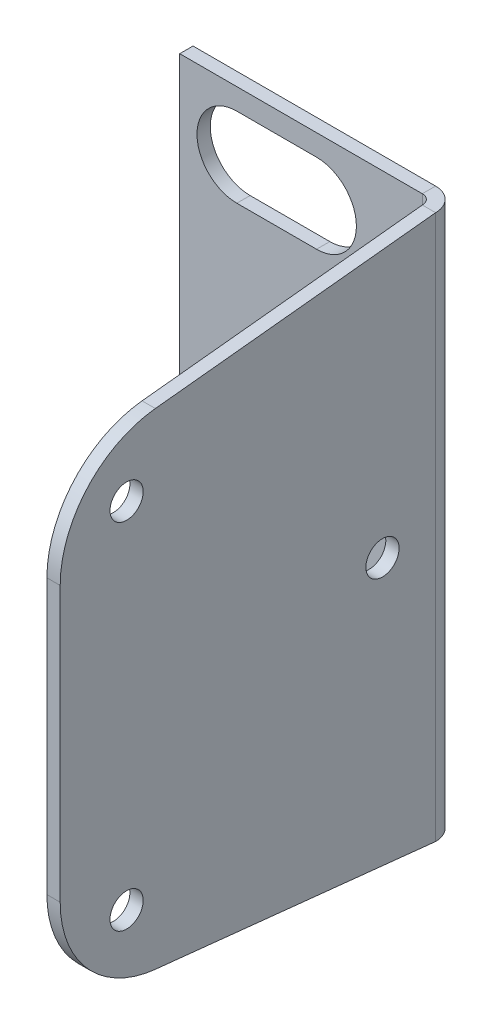
SolidWorks part; units mm, degrees
note: The reader was unsure of these and kept them because the rebuilt part matched: flange length of "Edge-Flange1".
ref_plane "Front Plane" through (0, 0, 0) normal (0, 0, 1) x (1, 0, 0)
ref_plane "Top Plane" through (0, 0, 0) normal (0, 1, 0) x (1, 0, 0)
ref_plane "Right Plane" through (0, 0, 0) normal (1, 0, 0) x (0, 0, -1)
sketch "Sketch1" plane through (0, 0, 0) normal (0, 0, 1) x (1, 0, 0)
  line L0 (-230.3, 22) -> (-230.3, -22) construction
  line L1 (-239.8, 20.5) -> (-219.8, 20.5)
  line L2 (-239.8, 20.5) -> (-239.8, 0)
  line L3 (-239.8, 0) -> (-219.8, 0)
  line L4 (-219.8, 20.5) -> (-219.8, 0)
  line L5 (-219.3, 22) -> (-241.3, 22) construction
  line L6 (-219.3, -22) -> (-241.3, -22) construction
  line L7 (-241.3, 22) -> (-241.3, -22) construction
  line L8 (-219.8, 19.2634) -> (-219.8, -19.2634) construction
  point P10 (-230.3, 0)
  dimension "D1" = 1.5
  dimension "D2" = 1.5
base flange "Base-Flange1" sketch "Sketch1" thickness 1 reverse thickness direction yes parameters "D1"=0.7366
edge flange "Edge-Flange1" sketch "Sketch8" flange angle 90 flange length 30 flange position material inside bend radius 0.7366 thickness 1 relief rectangular parameters "D6"=10
sketch "Sketch8" plane through (-219.8, 0, 1) normal (1, 0, 0) x (0, 1, 0)
  line L2 (0, 0) -> (0, 29)
  line L3 (0, 29) -> (20.5, 29)
  line L4 (20.5, 29) -> (20.5, 0)
  line L5 (0, 0) -> (20.5, 0) construction
  line L6 (0, 0) -> (20.5, 0)
bend "EdgeBend1" bend radius 0.7366 bend angle 90 parameters "D5"=1
sketch "Sketch9" plane through (-220.8, 0, 0) normal (-1, 0, 0) x (0, 0, 1)
  line L0 (1.7366, 20.5) -> (22.8362, 18.2823)
  line L1 (30, 20.5) -> (30, 0) construction
  line L2 (30, 10.3262) -> (30, 0)
  line L3 (1.7366, 20.5) -> (30, 20.5) construction
  arc A0 (30, 10.3262) -> (22.8362, 18.2823) centre (22, 10.3262) ccw
  point P9 (30, 17.5294)
  dimension "D1" = 8
  dimension "D2" = 6
extrude "Cut-Extrude1" cut sketch "Sketch9" against normal blind 10 and the other way through all
sketch "Sketch11" plane through (0, 0, 1) normal (0, 0, 1) x (1, 0, 0)
  line L0 (-229.5, 18.9) -> (-235.5, 18.9) construction
  line L1 (-235.5, 12.9) -> (-229.5, 12.9) construction
  line L2 (-229.5, 18.9) -> (-235.5, 18.9)
  line L3 (-235.5, 12.9) -> (-229.5, 12.9)
  arc A0 (-235.5, 18.9) -> (-235.5, 12.9) centre (-235.5, 15.9) ccw construction
  arc A1 (-229.5, 12.9) -> (-229.5, 18.9) centre (-229.5, 15.9) ccw construction
  arc A2 (-235.5, 18.9) -> (-235.5, 12.9) centre (-235.5, 15.9) ccw
  arc A3 (-229.5, 12.9) -> (-229.5, 18.9) centre (-229.5, 15.9) ccw
extrude "Cut-Extrude2" cut sketch "Sketch11" against normal blind 1 normal cut yes
mirror "Mirror1" about plane through (-239.8, 0, 1) normal (0, 1, 0) of bodies 104
hole_wizard "M3 Tapped Hole1" positions "Sketch13" profile "Sketch14" tap size "M3" standard "ISO" end condition through all
sketch "Sketch13" plane through (-220.8, 0, 0) normal (-1, 0, 0) x (0, 0, 1)
  line L0 (0, 0) -> (30, 0) construction
  line L1 (30, 10.3262) -> (30, -10.3262) construction
  line L2 (30, 10.3262) -> (22, 10.3262) construction
  line L3 (22, 10.3262) -> (25, 13.3262) construction
  line L4 (1.7366, -20.5) -> (1.7366, 20.5) construction
  point P0 (5.7366, 0)
  point P10 (25, 13.3262)
  point P30 (25, -13.3262)
  dimension "D3" = 4
  dimension "D1" = 45
  dimension "D2" = 5
sketch "Sketch14" plane through (-220.8, 0, 5.7366) normal (0, 1, 0) x (0, 0, 1)
  line L0 (0, 0) -> (0, 1)
  line L1 (0, 1) -> (1.25, 1)
  line L2 (1.25, 1) -> (1.25, 0)
  line L5 (1.25, 0) -> (0, 0)
  line L11 (0, -6.35) -> (0, 107.95) construction
  dimension "Thread Major Dia." = 2.5
  dimension "Thru Tap Drill Depth" = 1
sketch "Bend-Lines1" [suppressed] plane through (0, 0, 0) normal (0, 1, 0) x (1, 0, 0)
sketch "Bounding-Box1" [suppressed] plane through (0, 0, 0) normal (0, 1, 0) x (1, 0, 0)
sheet metal parameters "Sheet-Metal1" thickness 1 parameters "D1"=0.7366
flat pattern "Flat-Pattern1" [suppressed]
sketch "Bend-Lines2" plane through (0, 0, 0) normal (0, 1, 0) x (1, 0, 0)
sketch3d "Bounding-Box2" [suppressed]
  line L0 (-220.8, 20.5, 0) -> (-220.8, 0, 0) construction
  line L1 (-239.8, 20.5, 0) -> (-239.8, 0, 0) construction
  line L2 (-220.8, 20.5, 0) -> (-239.8, 20.5, 0) construction
  line L3 (-220.8, 0, 0) -> (-239.8, 0, 0) construction
sheet metal parameters "Sheet-Metal2" thickness 1 parameters "D1"=0.7366
flat pattern "Flat-Pattern1"
sketch "Bend-Lines2" plane through (0, 0, 0) normal (0, 0, -1) x (-1, 0, 0)
  line L0 (221.5654, 20.5) -> (221.5654, 0) construction
  line L1 (221.5654, 20.5) -> (221.5654, 0) construction
sketch3d "Bounding-Box2" [suppressed]
  line L0 (239.8, 0, 0) -> (192.3308, 0, 0) construction
  line L1 (239.8, 20.5, 0) -> (192.3308, 20.5, 0) construction
  line L2 (239.8, 0, 0) -> (239.8, 20.5, 0) construction
  line L3 (192.3308, 0, 0) -> (192.3308, 20.5, 0) construction
bend of the flat pattern "Flatten-<EdgeBend1>1"
sheet metal parameters "Sheet-Metal3" thickness 1 parameters "D1"=0.7366
flat pattern "Flat-Pattern1"
sketch "Bend-Lines2" plane through (0, 0, 0) normal (0, 0, -1) x (-1, 0, 0)
  line L0 (221.5654, 20.5) -> (221.5654, 0) construction
  line L1 (221.5654, 20.5) -> (221.5654, 0) construction
sketch3d "Bounding-Box2" [suppressed]
  line L0 (239.8, 0, 0) -> (192.3308, 0, 0) construction
  line L1 (239.8, 20.5, 0) -> (192.3308, 20.5, 0) construction
  line L2 (239.8, 0, 0) -> (239.8, 20.5, 0) construction
  line L3 (192.3308, 0, 0) -> (192.3308, 20.5, 0) construction
bend of the flat pattern "Flatten-<EdgeBend1>1"
sheet metal parameters "Sheet-Metal4" thickness 1 parameters "D1"=0.7366
flat pattern "Flat-Pattern1"
sketch "Bend-Lines2" plane through (0, 0, 0) normal (0, 0, -1) x (-1, 0, 0)
  line L0 (221.5654, 20.5) -> (221.5654, 0) construction
  line L1 (221.5654, 20.5) -> (221.5654, 0) construction
sketch3d "Bounding-Box2" [suppressed]
  line L0 (239.8, 0, 0) -> (192.3308, 0, 0) construction
  line L1 (239.8, 20.5, 0) -> (192.3308, 20.5, 0) construction
  line L2 (239.8, 0, 0) -> (239.8, 20.5, 0) construction
  line L3 (192.3308, 0, 0) -> (192.3308, 20.5, 0) construction
bend of the flat pattern "Flatten-<EdgeBend1>1"
sheet metal parameters "Sheet-Metal5" thickness 1 parameters "D1"=0.7366
flat pattern "Flat-Pattern5"
sketch "Bend-Lines3" plane through (0, 0, 0) normal (0, 0, -1) x (-1, 0, 0)
  line L0 (221.5654, 20.5) -> (221.5654, -20.5) construction
  line L1 (221.5654, 20.5) -> (221.5654, -20.5) construction
sketch3d "Bounding-Box3" [suppressed]
  line L0 (239.8, 20.5, 0) -> (192.3308, 20.5, 0) construction
  line L1 (239.8, -20.5, 0) -> (192.3308, -20.5, 0) construction
  line L2 (239.8, 20.5, 0) -> (239.8, -20.5, 0) construction
  line L3 (192.3308, 20.5, 0) -> (192.3308, -20.5, 0) construction
bend of the flat pattern "Flatten-<EdgeBend1>2"
sheet metal parameters "Sheet-Metal6" thickness 1 parameters "D1"=0.7366
flat pattern "Flat-Pattern5"
sketch "Bend-Lines3" plane through (0, 0, 0) normal (0, 0, -1) x (-1, 0, 0)
  line L0 (221.5654, 20.5) -> (221.5654, -20.5) construction
  line L1 (221.5654, 20.5) -> (221.5654, -20.5) construction
sketch3d "Bounding-Box3" [suppressed]
  line L0 (239.8, 20.5, 0) -> (192.3308, 20.5, 0) construction
  line L1 (239.8, -20.5, 0) -> (192.3308, -20.5, 0) construction
  line L2 (239.8, 20.5, 0) -> (239.8, -20.5, 0) construction
  line L3 (192.3308, 20.5, 0) -> (192.3308, -20.5, 0) construction
bend of the flat pattern "Flatten-<EdgeBend1>2"
equation "\"D2@Sketch1\"=\"D1@Sketch1\""
